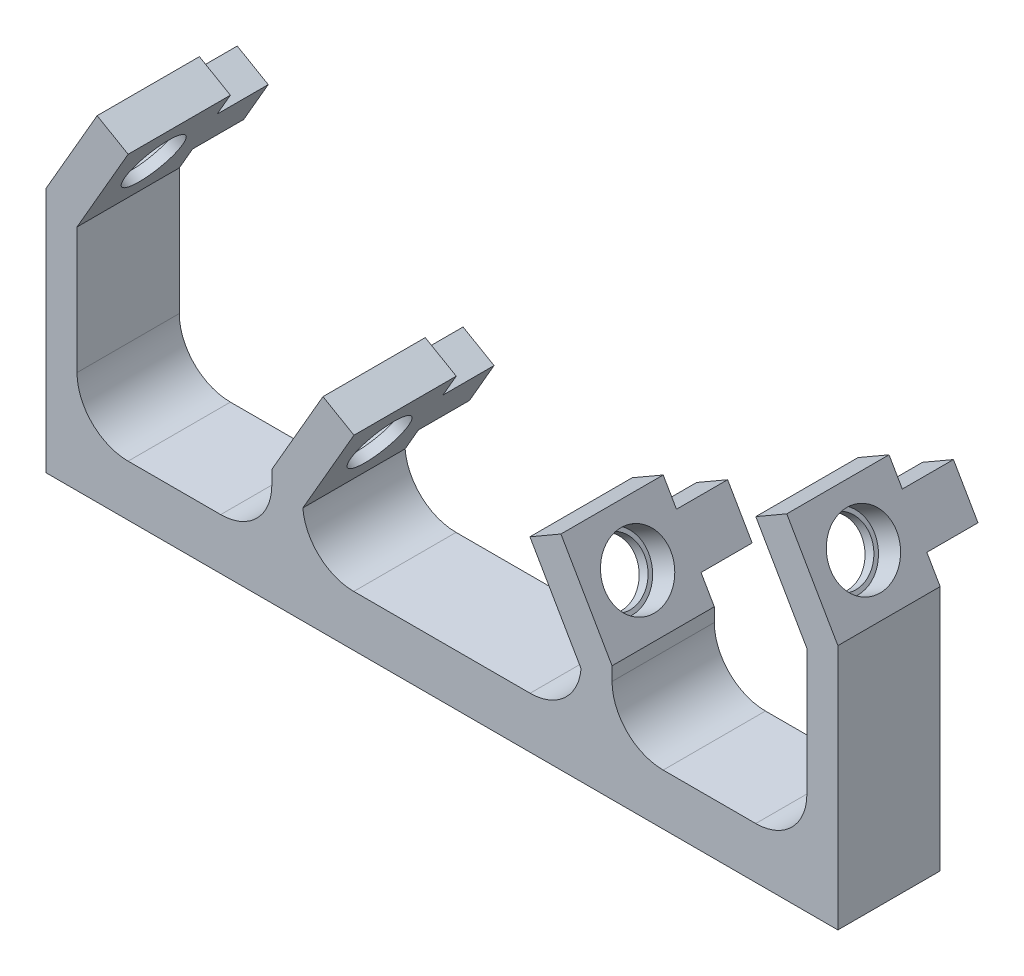
SolidWorks part; units mm, degrees
ref_plane "Plan de face" through (0, 0, 0) normal (0, 0, 1) x (1, 0, 0)
ref_plane "Plan de dessus" through (0, 0, 0) normal (0, 1, 0) x (1, 0, 0)
ref_plane "Plan de droite" through (0, 0, 0) normal (1, 0, 0) x (0, 0, -1)
sketch "Esquisse1" plane through (0, 0, 0) normal (0, 0, 1) x (1, 0, 0)
  line L0 (0, -83.388) -> (0, 83.388) construction
  line L1 (0, 0) -> (-75.8242, 43.7771) construction
  line L2 (0, 0) -> (94.8875, 54.7833) construction
  line L3 (59.641, 45.9808) -> (25, 25.9808) construction
  line L4 (25, 25.9808) -> (35, 8.6603) construction
  line L5 (35, 8.6603) -> (69.641, 28.6603) construction
  line L6 (59.641, 45.9808) -> (69.641, 28.6603) construction
  line L7 (-25, 25.9808) -> (-35, 8.6603) construction
  line L8 (-35, 8.6603) -> (-69.641, 28.6603) construction
  line L9 (-59.641, 45.9808) -> (-69.641, 28.6603) construction
  line L10 (-59.641, 45.9808) -> (-25, 25.9808) construction
  line L11 (23.2679, 24.9808) -> (33.2679, 7.6603)
  line L12 (61.3731, 46.9808) -> (71.3731, 29.6603)
  line L13 (33.2679, 7.6603) -> (33.2679, -5)
  line L14 (71.3731, 29.6603) -> (71.3731, -5)
  line L15 (71.3731, -15) -> (-71.3731, -15)
  line L16 (27.2058, -5) -> (-27.2058, -5)
  line L17 (23.2679, 24.9808) -> (17.2058, 21.4808)
  line L18 (17.2058, 21.4808) -> (27.2058, 4.1603)
  line L19 (27.2058, 4.1603) -> (27.2058, -5)
  line L20 (61.3731, 46.9808) -> (67.4352, 50.4808)
  line L21 (67.4352, 50.4808) -> (77.4352, 33.1603)
  line L22 (77.4352, 33.1603) -> (77.4352, -15)
  line L23 (77.4352, -15) -> (71.3731, -15)
  line L24 (33.2679, -5) -> (71.3731, -5)
  line L25 (-33.2679, -5) -> (-71.3731, -5)
  line L26 (-61.3731, 46.9808) -> (-71.3731, 29.6603)
  line L27 (-61.3731, 46.9808) -> (-67.4352, 50.4808)
  line L28 (-67.4352, 50.4808) -> (-77.4352, 33.1603)
  line L29 (-71.3731, 29.6603) -> (-71.3731, -5)
  line L30 (-77.4352, 33.1603) -> (-77.4352, -15)
  line L31 (-77.4352, -15) -> (-71.3731, -15)
  line L32 (-27.2058, 4.1603) -> (-27.2058, -5)
  line L33 (-33.2679, 7.6603) -> (-33.2679, -5)
  line L34 (-23.2679, 24.9808) -> (-33.2679, 7.6603)
  line L35 (-17.2058, 21.4808) -> (-27.2058, 4.1603)
  line L36 (-23.2679, 24.9808) -> (-17.2058, 21.4808)
  point P4 (0, 0)
  point P41 (0, -15)
  point P42 (0, -5)
  dimension "D1" = 60
  dimension "D2" = 60
  dimension "D3" = 20
  dimension "D4" = 10
  dimension "D5" = 40
  dimension "D6" = 25
  dimension "D9" = 7
  dimension "D10" = 10
  dimension "D12" = 7
extrude "Boss.-Extru.1" add sketch "Esquisse1" along normal mid plane 20
sketch "Esquisse2" plane through (-72.4352, 41.8205, 0) normal (-0.866, 0.5, 0) x (0, 0, 1)
  line L0 (10, 10) -> (-10, -10) construction
  circle A0 centre (0, 0) radius 6.5
  dimension "D1" = 13
extrude "Enlèv. mat.-Extru.1" cut sketch "Esquisse2" against normal blind 63
sketch "Esquisse3" plane through (72.4352, 41.8205, 0) normal (0.866, 0.5, 0) x (0, 0, -1)
  line L0 (10, 10) -> (-10, -10) construction
  circle A0 centre (0, 0) radius 6.5
  dimension "D1" = 13
extrude "Enlèv. mat.-Extru.2" cut sketch "Esquisse3" against normal blind 63
fillet "Congé1" radius 10 4 edges at (-71.3731, -5, 0) (71.3731, -5, 0) (33.2679, -5, 0) (-33.2679, -5, 0)
fillet "Congé2" radius 10 2 edges at (-27.2058, -5, 0) (27.2058, -5, 0)
sketch "Esquisse4" plane through (-22.2058, 12.8205, 0) normal (0.866, -0.5, 0) x (0, 0, -1)
  circle A0 centre (0, 0) radius 6.5 construction
  circle A1 centre (0, 0) radius 6.5
  circle A2 centre (0, 0) radius 5.7
  dimension "D1" = 11.4
extrude "Boss.-Extru.2" add sketch "Esquisse4" against normal blind 2
sketch "Esquisse5" plane through (-66.3731, 38.3205, 0) normal (0.866, -0.5, 0) x (0, 0, -1)
  circle A0 centre (0, 0) radius 6.5 construction
  circle A1 centre (0, 0) radius 6.5
  circle A2 centre (0, 0) radius 5.7
  dimension "D1" = 11.4
extrude "Boss.-Extru.3" add sketch "Esquisse5" against normal blind 2
sketch "Esquisse6" plane through (22.2058, 12.8205, 0) normal (-0.866, -0.5, 0) x (0, 0, 1)
  circle A0 centre (0, 0) radius 6.5 construction
  circle A1 centre (0, 0) radius 6.5
  circle A2 centre (0, 0) radius 5.7
  dimension "D1" = 11.4
extrude "Boss.-Extru.4" add sketch "Esquisse6" against normal blind 2
sketch "Esquisse7" plane through (66.3731, 38.3205, 0) normal (-0.866, -0.5, 0) x (0, 0, 1)
  circle A0 centre (0, 0) radius 6.5 construction
  circle A1 centre (0, 0) radius 6.5
  circle A2 centre (0, 0) radius 5.7
  dimension "D1" = 11.4
extrude "Boss.-Extru.5" add sketch "Esquisse7" against normal blind 2
sketch "Esquisse8" plane through (0, 0, -10) normal (0, 0, -1) x (-1, 0, 0)
  line L1 (61.3731, 46.9808) -> (67.4352, 50.4808) construction
  line L8 (63.9731, 42.4774) -> (70.0352, 45.9774)
  line L9 (19.8058, 16.9774) -> (25.8679, 20.4774)
  line L10 (-25.8679, 20.4774) -> (-19.8058, 16.9774)
  line L11 (-70.0352, 45.9774) -> (-63.9731, 42.4774)
  line L12 (68.7731, 34.1636) -> (74.8352, 37.6636)
  line L13 (24.6058, 8.6636) -> (30.6679, 12.1636)
  line L14 (-30.6679, 12.1636) -> (-24.6058, 8.6636)
  line L15 (-74.8352, 37.6636) -> (-68.7731, 34.1636)
  line L16 (-61.3731, 46.9808) -> (-71.3731, 29.6603) construction
  line L17 (-77.4352, 33.1603) -> (-67.4352, 50.4808) construction
  line L18 (-33.2679, 7.6603) -> (-23.2679, 24.9808) construction
  line L19 (-17.2058, 21.4808) -> (-27.2058, 4.1603) construction
  line L20 (27.2058, 4.1603) -> (17.2058, 21.4808) construction
  line L21 (23.2679, 24.9808) -> (33.2679, 7.6603) construction
  line L22 (67.4352, 50.4808) -> (77.4352, 33.1603) construction
  line L23 (71.3731, 29.6603) -> (61.3731, 46.9808) construction
  line L24 (-63.9731, 42.4774) -> (-68.7731, 34.1636)
  line L25 (-74.8352, 37.6636) -> (-70.0352, 45.9774)
  line L26 (-30.6679, 12.1636) -> (-25.8679, 20.4774)
  line L27 (-19.8058, 16.9774) -> (-24.6058, 8.6636)
  line L28 (24.6058, 8.6636) -> (19.8058, 16.9774)
  line L29 (25.8679, 20.4774) -> (30.6679, 12.1636)
  line L30 (70.0352, 45.9774) -> (74.8352, 37.6636)
  line L31 (68.7731, 34.1636) -> (63.9731, 42.4774)
  dimension "D1" = 5.2
  dimension "D2" = 9.6
extrude "Boss.-Extru.6" add sketch "Esquisse8" along normal blind 10
equation "\"è\"=27.1324"
